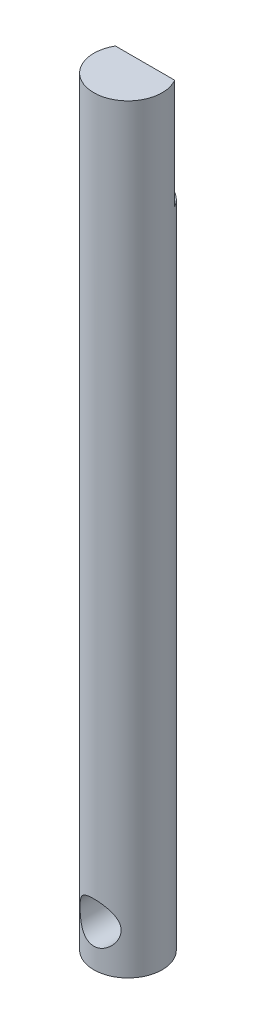
SolidWorks part; units mm, degrees
material "Plain Carbon Steel"
ref_plane "Front Plane" through (0, 0, 0) normal (0, 0, 1) x (1, 0, 0)
ref_plane "Top Plane" through (0, 0, 0) normal (0, 1, 0) x (1, 0, 0)
ref_plane "Right Plane" through (0, 0, 0) normal (1, 0, 0) x (0, 0, -1)
sketch "Sketch1" plane through (0, 0, 0) normal (0, 1, 0) x (1, 0, 0)
  circle A0 centre (0, 0) radius 3.9688
extrude "Boss-Extrude1" add sketch "Sketch1" along normal blind 88.138
sketch "Sketch2" plane through (0, 88.138, 0) normal (0, 1, 0) x (1, 0, 0)
  line L0 (0, 0) -> (3.437, 1.9844) construction
  line L1 (3.437, 1.9844) -> (-3.437, 1.9844)
  line L2 (-3.437, 1.9844) -> (0, 0) construction
  line L3 (-3.437, 1.9844) -> (-4.7194, 2.5225)
  line L4 (-4.7194, 2.5225) -> (-2.5902, 6.3532)
  line L5 (-2.5902, 6.3532) -> (2.4567, 4.7289)
  line L6 (2.4567, 4.7289) -> (3.437, 1.9844)
  circle A1 centre (0, 0) radius 3.9688 construction
  point P2 (0, 1.9844)
  dimension "D1" = 120
extrude "Cut-Extrude1" cut sketch "Sketch2" against normal blind 12.7
sketch "Sketch3" plane through (0, 0, -1.9844) normal (0, 0, -1) x (-1, 0, 0)
  line L0 (0, 0) -> (0, 9.525) construction
  circle A0 centre (0, 4.7625) radius 2.3813
  dimension "D2" = 4.7625
  dimension "D1" = 9.525
extrude "Cut-Extrude2" cut sketch "Sketch3" against normal blind 12.7 and the other way blind 12.7
